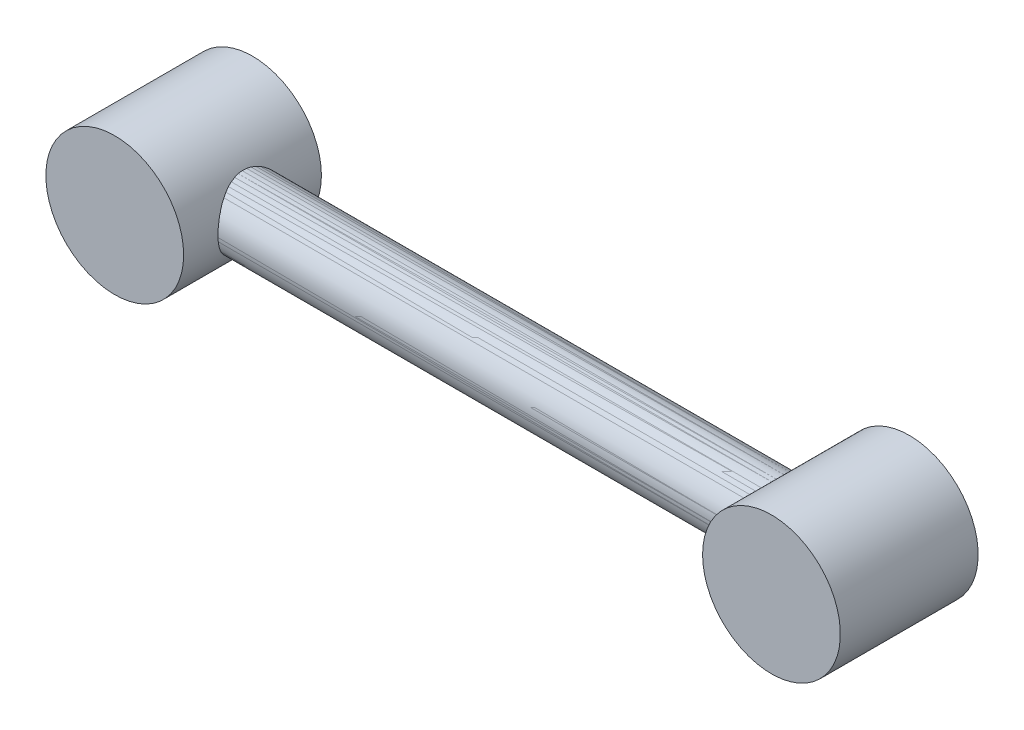
SolidWorks part; units mm, degrees
ref_plane "Front Plane" through (0, 0, 0) normal (0, 0, 1) x (1, 0, 0)
ref_plane "Top Plane" through (0, 0, 0) normal (0, 1, 0) x (1, 0, 0)
ref_plane "Right Plane" through (0, 0, 0) normal (1, 0, 0) x (0, 0, -1)
sketch "Sketch1" plane through (0, 0, 0) normal (1, 0, 0) x (0, 0, -1)
  circle A0 centre (0, 0) radius 5
  dimension "D1" = 10
extrude "Boss-Extrude1" add sketch "Sketch1" along normal blind 80
sketch "Sketch2" plane through (0, 0, 0) normal (0, 0, 1) x (1, 0, 0)
  circle A0 centre (-7.666, 0) radius 10
  dimension "D1" = 20
extrude "Boss-Extrude2" add sketch "Sketch2" along normal blind 10 and the other way blind 10 separate body
sketch "Sketch3" plane through (0, 0, 0) normal (0, 1, 0) x (1, 0, 0)
  line L0 (-7.666, 10) -> (-7.666, -10) construction
  circle A0 centre (-7.666, 0) radius 3.9882
ref_plane "Plane1" through (0, -224, 0) normal (0, 1, 0) x (1, 0, 0)
mirror "Mirror1" about plane through (0, -224, 0) normal (0, 1, 0) of bodies 101 102 103
ref_plane "Plane2" through (40, 0, 0) normal (-1, 0, 0) x (0, 0, 1)
mirror "Mirror2" about plane through (40, 0, 0) normal (-1, 0, 0) of bodies 101 104 105 102 103
ref_axis "Axis1" through (80, 0, 0) along (-1, 0, 0)
delete or keep bodies "Body-Delete/Keep 1" type delete bodies bodies 108 105 107 104
